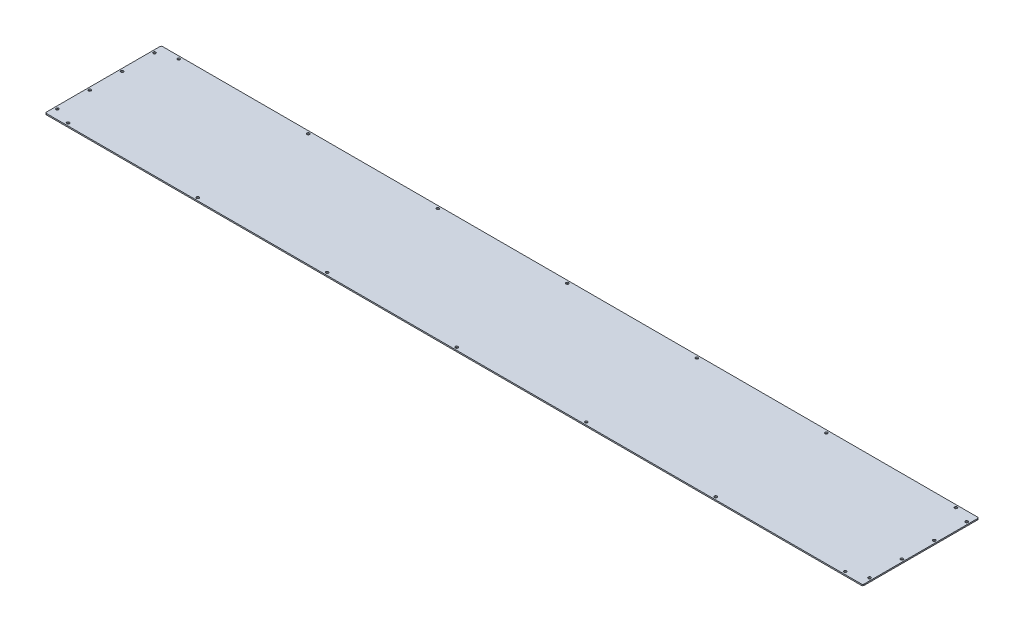
SolidWorks part; units mm, degrees
material "PC High Viscosity"
ref_plane "Front Plane" through (0, 0, 0) normal (0, 0, 1) x (1, 0, 0)
ref_plane "Top Plane" through (0, 0, 0) normal (0, 1, 0) x (1, 0, 0)
ref_plane "Right Plane" through (0, 0, 0) normal (1, 0, 0) x (0, 0, -1)
sketch "Sketch1" plane through (0, 0, 0) normal (0, 1, 0) x (1, 0, 0)
  line L1 (-962.025, 136.525) -> (962.025, 136.525)
  line L2 (-962.025, 136.525) -> (-962.025, -136.525)
  line L3 (-962.025, -136.525) -> (962.025, -136.525)
  line L4 (962.025, 136.525) -> (962.025, -136.525)
  line L5 (-962.025, 136.525) -> (962.025, -136.525) construction
  line L6 (-962.025, -136.525) -> (962.025, 136.525) construction
  point P0 (0, 0)
  dimension "D1" = 1924.05
  dimension "D2" = 273.05
extrude "Boss-Extrude1" add sketch "Sketch1" along normal blind 2.9972
fillet "Fillet1" radius 3.175 4 edges at (962.025, 1.4986, 136.525) (962.025, 1.4986, -136.525) (-962.025, 1.4986, 136.525) (-962.025, 1.4986, -136.525)
hole_wizard "1/4 (0.25) Diameter Hole1" positions "Sketch2" profile "Sketch3" hole size "1/4" standard "ANSI Inch" end condition through all
sketch "Sketch2" plane through (0, 2.9972, 0) normal (0, 1, 0) x (1, 0, 0)
  line L0 (-955.675, -38.1) -> (-955.675, -114.3) construction
  line L2 (-955.675, 38.1) -> (-955.675, -38.1) construction
  line L4 (-914.4, -130.175) -> (-609.6, -130.175) construction
  line L5 (-609.6, -130.175) -> (-304.8, -130.175) construction
  line L6 (-304.8, -130.175) -> (0, -130.175) construction
  line L7 (0, -130.175) -> (304.8, -130.175) construction
  line L8 (304.8, -130.175) -> (609.6, -130.175) construction
  line L9 (609.6, -130.175) -> (914.4, -130.175) construction
  line L11 (-958.85, -136.525) -> (958.85, -136.525) construction
  line L12 (-962.025, 133.35) -> (-962.025, -133.35) construction
  line L13 (0, 136.525) -> (0, -136.525) construction
  line L14 (958.85, 136.525) -> (-958.85, 136.525) construction
  line L16 (-962.025, 0) -> (962.025, 0) construction
  line L17 (962.025, -133.35) -> (962.025, 133.35) construction
  line L19 (609.6, 130.175) -> (914.4, 130.175) construction
  line L20 (304.8, 130.175) -> (609.6, 130.175) construction
  line L21 (0, 130.175) -> (304.8, 130.175) construction
  line L22 (-304.8, 130.175) -> (0, 130.175) construction
  line L23 (-609.6, 130.175) -> (-304.8, 130.175) construction
  line L24 (-914.4, 130.175) -> (-609.6, 130.175) construction
  line L25 (955.675, 38.1) -> (955.675, -38.1) construction
  line L26 (955.675, -38.1) -> (955.675, -114.3) construction
  line L27 (-955.675, 114.3) -> (-955.675, 38.1) construction
  point P0 (0, -130.175)
  point P2 (-955.675, 38.1)
  point P4 (-955.675, -38.1)
  point P6 (-914.4, -130.175)
  point P8 (-609.6, -130.175)
  point P10 (-304.8, -130.175)
  point P12 (304.8, -130.175)
  point P14 (609.6, -130.175)
  point P16 (914.4, -130.175)
  point P24 (-955.675, -114.3)
  point P66 (914.4, 130.175)
  point P67 (609.6, 130.175)
  point P68 (304.8, 130.175)
  point P69 (-304.8, 130.175)
  point P70 (-609.6, 130.175)
  point P71 (-914.4, 130.175)
  point P72 (0, 130.175)
  point P76 (955.675, -114.3)
  point P77 (955.675, -38.1)
  point P78 (955.675, 38.1)
  point P80 (-955.675, 114.3)
  point P86 (955.675, 114.3)
  dimension "D1" = 304.8
  dimension "D2" = 6.35
  dimension "D3" = 6.35
  dimension "D4" = 76.2
  dimension "D5" = 38.1
sketch "Sketch3" plane through (0, 2.9972, 130.175) normal (1, 0, 0) x (0, 0, 1)
  line L0 (0, 0) -> (0, 2.9972)
  line L1 (0, 2.9972) -> (3.175, 2.9972)
  line L2 (3.175, 2.9972) -> (3.175, 0)
  line L5 (3.175, 0) -> (0, 0)
  line L11 (0, -6.35) -> (0, 107.95) construction
  dimension "Thru Hole Dia." = 6.35
  dimension "Thru Hole Depth" = 2.9972
